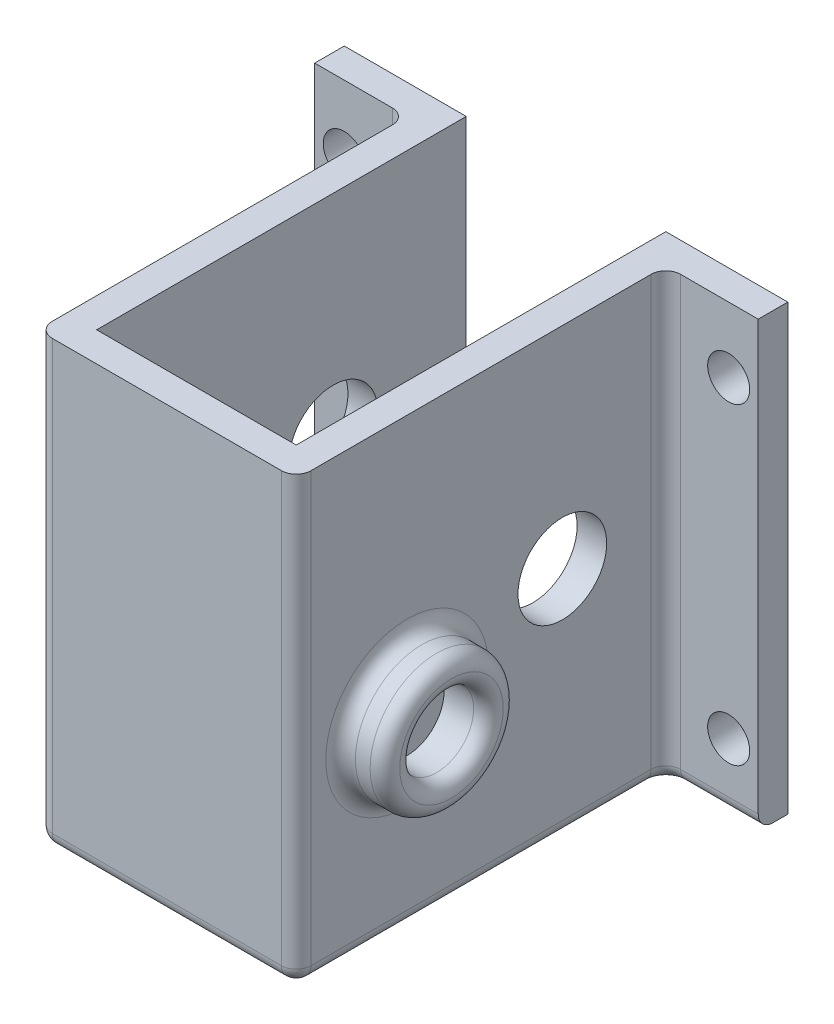
SolidWorks part; units mm, degrees
ref_plane "Front Plane" through (0, 0, 0) normal (0, 0, 1) x (1, 0, 0)
ref_plane "Top Plane" through (0, 0, 0) normal (0, 1, 0) x (1, 0, 0)
ref_plane "Right Plane" through (0, 0, 0) normal (1, 0, 0) x (0, 0, -1)
sketch "Sketch1" plane through (0, 0, 0) normal (0, 1, 0) x (1, 0, 0)
  line L1 (8.75, -13.5) -> (-8.75, -13.5)
  line L2 (8.75, -13.5) -> (8.75, 13.5)
  line L3 (8.75, 13.5) -> (-8.75, 13.5)
  line L4 (-8.75, -13.5) -> (-8.75, 13.5)
  line L5 (8.75, -13.5) -> (-8.75, 13.5) construction
  line L6 (8.75, 13.5) -> (-8.75, -13.5) construction
  point P0 (0, 0)
  dimension "D1" = 17.5
  dimension "D2" = 27
extrude "Boss-Extrude1" add sketch "Sketch1" along normal blind 2
sketch "Sketch2" plane through (0, 2, 0) normal (0, 1, 0) x (1, 0, 0)
  line L0 (-8.75, 13.5) -> (-8.75, -13.5)
  line L1 (-8.75, -13.5) -> (8.75, -13.5)
  line L2 (8.75, -13.5) -> (8.75, 13.5)
  line L3 (-6.75, 13.5) -> (-6.75, -11.5)
  line L4 (-6.75, -11.5) -> (6.75, -11.5)
  line L5 (6.75, -11.5) -> (6.75, 13.5)
  line L6 (-8.75, 13.5) -> (-6.75, 13.5)
  line L7 (6.75, 13.5) -> (8.75, 13.5)
  dimension "D1" = 2
extrude "Boss-Extrude2" add sketch "Sketch2" along normal blind 28
sketch "Sketch3" plane through (-8.75, 0, 0) normal (-1, 0, 0) x (0, 0, 1)
  line L0 (-13.5, 0) -> (13.5, 0) construction
  line L1 (-13.5, 30) -> (-11.5, 30)
  line L2 (-13.5, 30) -> (-13.5, 0)
  line L3 (-13.5, 0) -> (-11.5, 0)
  line L4 (-11.5, 30) -> (-11.5, 0)
  dimension "D1" = 2
extrude "Boss-Extrude3" add sketch "Sketch3" along normal blind 6.25
mirror "Mirror1" about plane through (0, 0, 0) normal (1, 0, 0) of "Boss-Extrude3"
sketch "Sketch4" plane through (-8.75, 0, 0) normal (-1, 0, 0) x (0, 0, 1)
  line L0 (13.5, 30) -> (13.5, 0) construction
  circle A0 centre (-4.5, 15.76) radius 3
  dimension "D3" = 6
  dimension "D1" = 15.76
  dimension "D2" = 18
extrude "Cut-Extrude1" cut sketch "Sketch4" against normal through all both and the other way through all contours A0
sketch "Sketch5" plane through (0, 2, 0) normal (0, 1, 0) x (1, 0, 0)
  line L0 (-8.75, 11.5) -> (-8.75, -13.5) construction
  line L2 (-8.75, -13.5) -> (8.75, -13.5) construction
  circle A0 centre (3.4, -2.5) radius 3
  dimension "D1" = 6
  dimension "D2" = 12.15
  dimension "D3" = 11
extrude "Cut-Extrude2" cut sketch "Sketch5" against normal through all both and the other way through all
hole_wizard "#33 (0.113) Diameter Hole1" positions "Sketch7" profile "Sketch8" hole size "#33" standard "ANSI Inch" end condition through all
sketch "Sketch7" plane through (0, 0, -11.5) normal (0, 0, 1) x (1, 0, 0)
  line L2 (15, 30) -> (15, 0) construction
  line L3 (-15, 30) -> (-15, 0) construction
  line L4 (-6.75, 30) -> (-15, 30) construction
  point P0 (-13, 25.5776)
  point P3 (-13, 4.4224)
  point P6 (13, 4.4224)
  point P9 (13, 25.5776)
  dimension "D1" = 2
  dimension "D2" = 2
  dimension "D3" = 4.4224
  dimension "D4" = 21.1552
sketch "Sketch8" plane through (-13, 25.5776, -11.5) normal (1, 0, 0) x (0, -1, 0)
  line L0 (0, 0) -> (0, 2)
  line L1 (0, 2) -> (1.4224, 2)
  line L2 (1.4224, 2) -> (1.4224, 0)
  line L5 (1.4224, 0) -> (0, 0)
  line L11 (0, -6.35) -> (0, 107.95) construction
  dimension "Thru Hole Dia." = 2.8448
  dimension "Thru Hole Depth" = 2
sketch "Sketch9" plane through (8.75, 0, 0) normal (1, 0, 0) x (0, 0, -1)
  line L0 (-13.5, 0) -> (11.5, 0) construction
  line L1 (13.5, 30) -> (13.5, 0) construction
  circle A0 centre (-6, 12.56) radius 2.5
  circle A1 centre (-6, 12.56) radius 4.5
  dimension "D1" = 5
  dimension "D2" = 9
  dimension "D3" = 12.56
  dimension "D4" = 19.5
extrude "Boss-Extrude4" add sketch "Sketch9" along normal blind 3
sketch "Sketch10" plane through (8.75, 0, 0) normal (1, 0, 0) x (0, 0, -1)
  circle A0 centre (-6, 12.56) radius 0.5
  dimension "D1" = 1
extrude "Cut-Extrude3" cut sketch "Sketch10" against normal up to surface (2 mm away) up to face at (6.75, 15.76, -7.5)
fillet "Fillet1" radius 1 12 edges at (11.875, 0, -11.5) (-11.875, 0, -11.5) (8.75, 15, -11.5) (-8.75, 15, -11.5) (-8.75, 0, 1) (8.75, 0, 1) (0, 0, 13.5) (-8.75, 15, 13.5) (8.75, 15, 13.5) (11.75, 12.56, 3.5) (11.75, 12.56, 1.5) (8.75, 12.56, 10.5)
